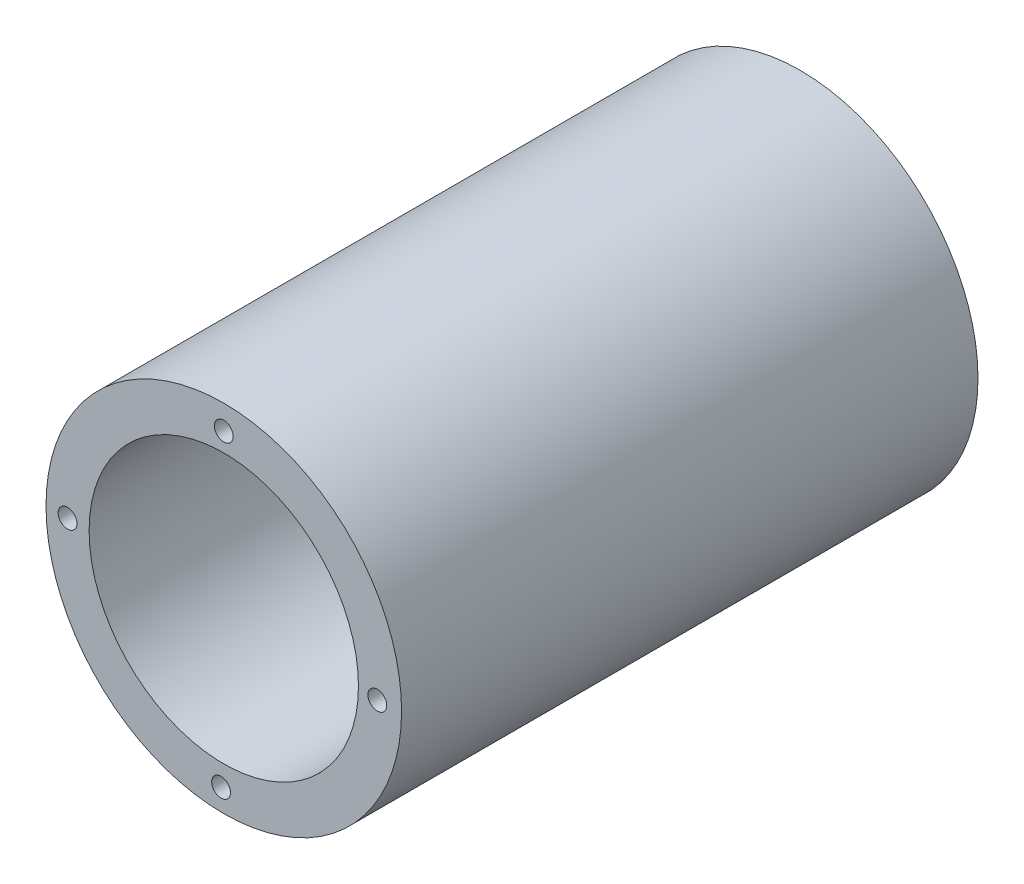
SolidWorks part; units mm, degrees
ref_plane "Alzado" through (0, 0, 0) normal (0, 0, 1) x (1, 0, 0)
ref_plane "Planta" through (0, 0, 0) normal (0, 1, 0) x (1, 0, 0)
ref_plane "Vista lateral" through (0, 0, 0) normal (1, 0, 0) x (0, 0, -1)
sketch "Croquis1" plane through (0, 0, 0) normal (0, 0, 1) x (1, 0, 0)
  circle A0 centre (0, 0) radius 33
  circle A1 centre (0, 0) radius 25
  dimension "D1" = 66
  dimension "D2" = 8
extrude "Boss-Extrude1" add sketch "Croquis1" along normal blind 107
sketch "Sketch1" plane through (0, 0, 0) normal (0, 0, -1) x (-1, 0, 0)
  line L0 (0, 0) -> (11.3818, 0) construction
  circle A0 centre (-29, 0) radius 1.5
  circle A1 centre (0, 29) radius 1.5
  circle A2 centre (29, 0) radius 1.5
  circle A3 centre (0, -29) radius 1.5
  circle A7 centre (0, 0) radius 29 construction
  circle A8 centre (0, 0) radius 25 construction
  point P17 (0, 0)
  dimension "D1" = 4
  dimension "D2" = 3
  dimension "D3" = 0
  dimension "D4" = 4
extrude "Cut-Extrude1" cut sketch "Sketch1" against normal blind 5
sketch "Sketch2" plane through (0, 0, 107) normal (0, 0, 1) x (1, 0, 0)
  circle A0 centre (-29, 0) radius 1.75
  circle A2 centre (0, 0) radius 29 construction
  circle A3 centre (0, 0) radius 25 construction
  circle A4 centre (0, 28.5) radius 1.75
  circle A5 centre (28.5, -0.5) radius 1.75
  circle A6 centre (-0.5, -29) radius 1.75
  point P16 (-0.25, -0.25)
  dimension "D1" = 4
  dimension "D2" = 3.5
  dimension "D3" = 4
extrude "Cut-Extrude2" cut sketch "Sketch2" against normal blind 5
